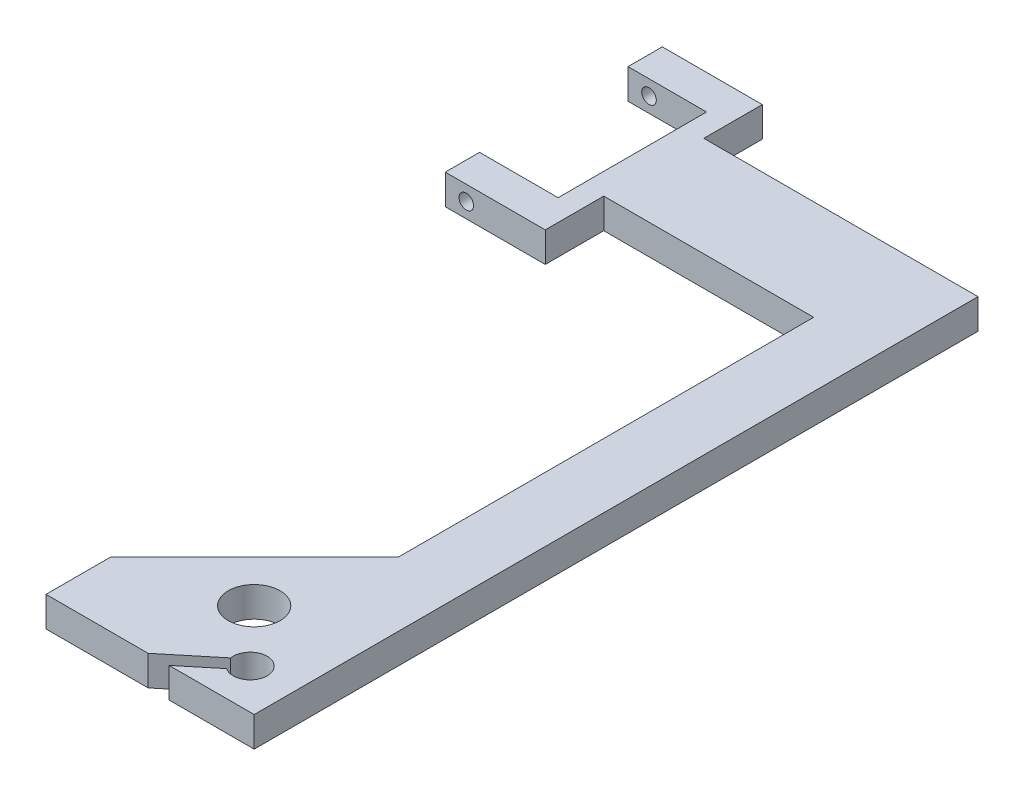
SolidWorks part; units mm, degrees
ref_plane "Front Plane" through (0, 0, 0) normal (0, 0, 1) x (1, 0, 0)
ref_plane "Top Plane" through (0, 0, 0) normal (0, 1, 0) x (1, 0, 0)
ref_plane "Right Plane" through (0, 0, 0) normal (1, 0, 0) x (0, 0, -1)
sketch "Sketch1" plane through (0, 0, 0) normal (0, 1, 0) x (1, 0, 0)
  line L14 (23.34, 33.5948) -> (23.34, 19.9448)
  line L15 (23.34, 19.9448) -> (0, 19.9448)
  line L16 (0, 19.9448) -> (0, 27.9448)
  line L17 (0, 27.9448) -> (18.34, 27.9448)
  line L18 (18.34, 27.9448) -> (18.34, 62.5948)
  line L19 (18.34, 62.5948) -> (0, 62.5948)
  line L20 (0, 62.5948) -> (0, 70.5948)
  line L21 (0, 70.5948) -> (23.34, 70.5948)
  line L22 (23.34, 70.5948) -> (23.34, 56.9448)
  line L28 (23.34, 33.5948) -> (72.34, 33.5948)
  line L29 (72.34, 33.5948) -> (72.34, -63.4052)
  line L30 (23.34, 56.9448) -> (87.34, 56.9448)
  line L31 (87.34, 56.9448) -> (87.34, -63.4052)
  line L32 (72.34, -63.4052) -> (38.75, -96.9952)
  line L34 (87.34, -111.9952) -> (87.34, -63.4052)
  line L35 (73.1495, -103.293) -> (62.5726, -111.9952)
  line L36 (67.475, -111.9952) -> (74.8367, -105.9383)
  line L37 (67.475, -111.9952) -> (87.34, -111.9952)
  line L38 (62.5726, -111.9952) -> (38.75, -111.9952)
  line L39 (38.75, -96.9952) -> (38.75, -111.9952)
  circle A2 centre (65.34, -89.9952) radius 6.05
  arc A3 (74.8367, -105.9383) -> (73.1495, -103.293) centre (77.0658, -102.6558) ccw
  point P0 (74.8367, -105.9383)
  dimension "D11" = 7
  dimension "D13" = 12.1
  dimension "D2" = 34.65
  dimension "D3" = 8
  dimension "D8" = 15
  dimension "D14" = 4.9023
extrude "Boss-Extrude1" add sketch "Sketch1" along normal blind 7
sketch "Sketch2" plane through (0, 0, -19.9448) normal (0, 0, 1) x (1, 0, 0)
  line L0 (0, 7) -> (0, 0) construction
  line L1 (0, 7) -> (23.34, 7) construction
  line L3 (0, 0) -> (23.34, 0) construction
  circle A0 centre (4.9, 3.5) radius 1.7
  dimension "D1" = 3.4
  dimension "D2" = 4.9
  dimension "D3" = 3.5
  dimension "D4" = 3.5
extrude "Cut-Extrude1" cut sketch "Sketch2" against normal blind 60
